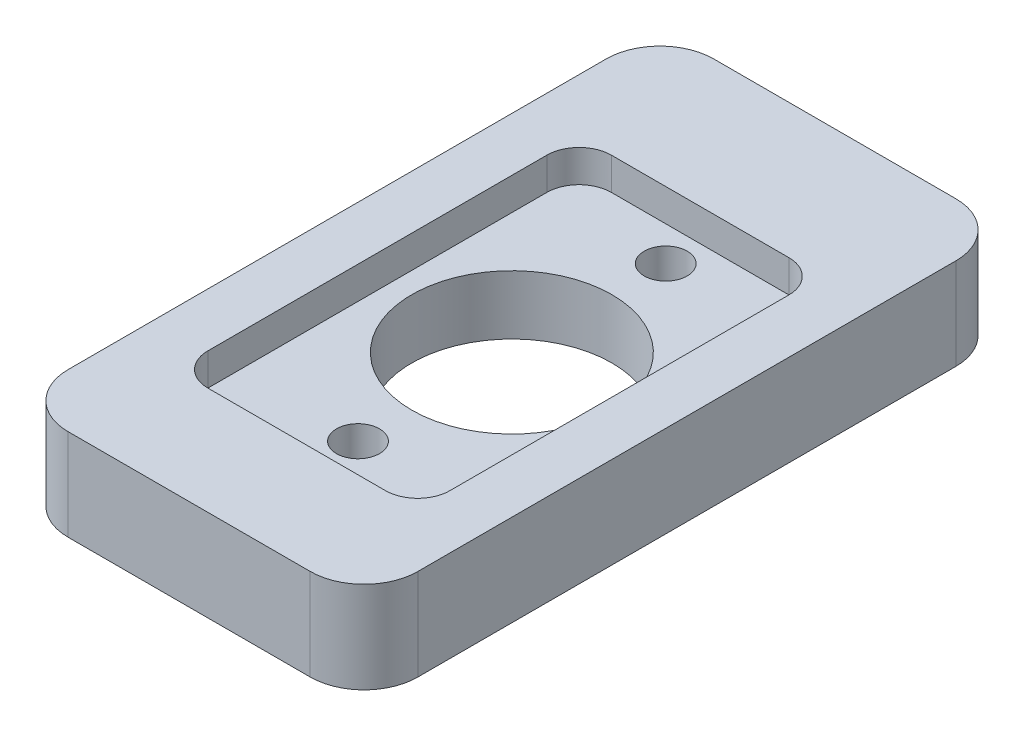
SolidWorks part; units mm, degrees
ref_plane "Front Plane" through (0, 0, 0) normal (0, 0, 1) x (1, 0, 0)
ref_plane "Top Plane" through (0, 0, 0) normal (0, 1, 0) x (1, 0, 0)
ref_plane "Right Plane" through (0, 0, 0) normal (1, 0, 0) x (0, 0, -1)
sketch "Sketch1" plane through (0, 0, 0) normal (0, 1, 0) x (1, 0, 0)
  line L1 (2, 0) -> (11, 0)
  line L2 (0, -2) -> (0, -22)
  line L3 (2, -24) -> (11, -24)
  line L4 (13, -2) -> (13, -22)
  arc A0 (0, -22) -> (2, -24) centre (2, -22) ccw
  arc A1 (11, -24) -> (13, -22) centre (11, -22) ccw
  arc A2 (11, 0) -> (13, -2) centre (11, -2) cw
  arc A3 (2, 0) -> (0, -2) centre (2, -2) ccw
  point P7 (0, -24)
  point P12 (13, 0)
  point P15 (0, 0)
  dimension "D3" = 2
  dimension "D1" = 13
  dimension "D2" = 24
extrude "Boss-Extrude1" add sketch "Sketch1" along normal blind 3.4
sketch "Sketch2" plane through (0, 3.4, 0) normal (0, 1, 0) x (1, 0, 0)
  line L0 (11, 0) -> (2, 0) construction
  line L1 (3.1947, -5) -> (9.7947, -5)
  line L2 (1.9947, -6.2) -> (1.9947, -18.8)
  line L3 (3.1947, -20) -> (9.7947, -20)
  line L4 (10.9947, -6.2) -> (10.9947, -18.8)
  arc A0 (1.9947, -18.8) -> (3.1947, -20) centre (3.1947, -18.8) ccw
  arc A1 (9.7947, -20) -> (10.9947, -18.8) centre (9.7947, -18.8) ccw
  arc A2 (9.7947, -5) -> (10.9947, -6.2) centre (9.7947, -6.2) cw
  arc A3 (3.1947, -5) -> (1.9947, -6.2) centre (3.1947, -6.2) ccw
  point P4 (6.4947, -5)
  point P9 (1.9947, -20)
  point P14 (10.9947, -5)
  point P17 (1.9947, -5)
  dimension "D4" = 1.2
  dimension "D1" = 9
  dimension "D2" = 15
  dimension "D3" = 5
extrude "Cut-Extrude1" cut sketch "Sketch2" against normal blind 1.2
sketch "Sketch3" plane through (0, 2.2, 0) normal (0, 1, 0) x (1, 0, 0)
  line L0 (10.9947, -18.8) -> (10.9947, -6.2) construction
  line L2 (3.1947, -20) -> (9.7947, -20) construction
  circle A0 centre (6.4947, -12) radius 3.72
  circle A1 centre (6.4947, -6.28) radius 0.8
  circle A2 centre (6.4947, -17.72) radius 0.8
  dimension "D1" = 7.44
  dimension "D4" = 2
  dimension "D2" = 4.5
  dimension "D3" = 8
  dimension "D5" = 2
extrude "Cut-Extrude2" cut sketch "Sketch3" against normal through all
